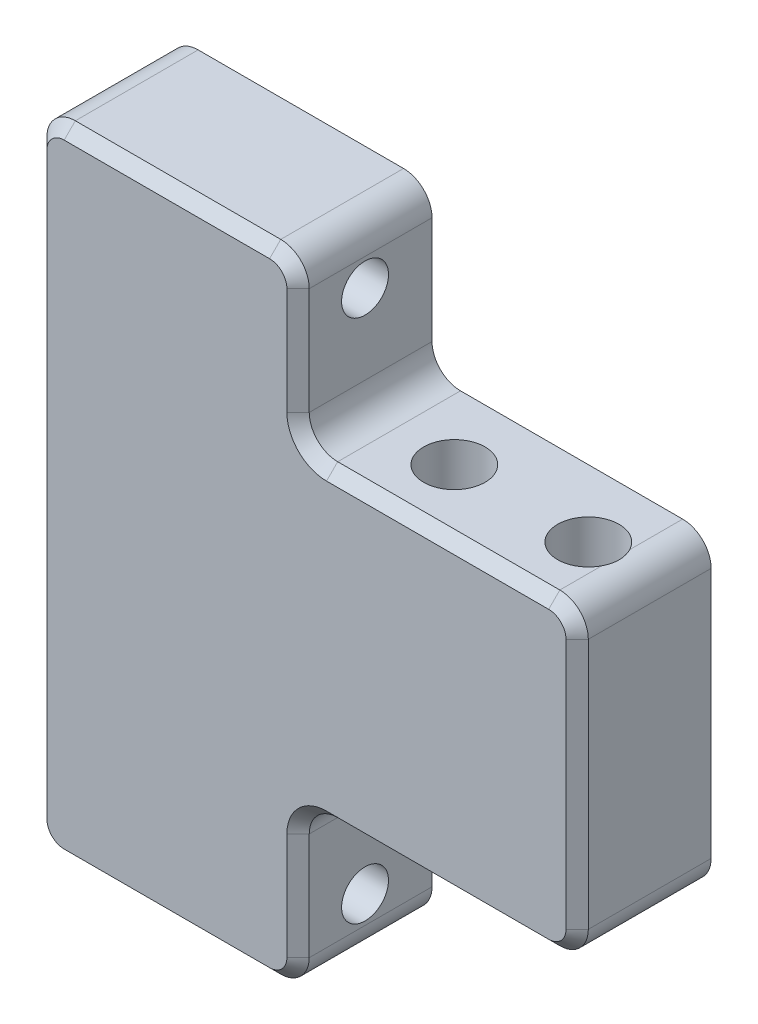
SolidWorks part; units mm, degrees
ref_plane "Front Plane" through (0, 0, 0) normal (0, 0, 1) x (1, 0, 0)
ref_plane "Top Plane" through (0, 0, 0) normal (0, 1, 0) x (1, 0, 0)
ref_plane "Right Plane" through (0, 0, 0) normal (1, 0, 0) x (0, 0, -1)
sketch "Sketch1" plane through (0, 0, 0) normal (0, 0, 1) x (1, 0, 0)
  line L7 (10, 65) -> (10, 8)
  line L9 (33.5, 50.3) -> (33.5, 65)
  line L10 (33.5, 50.3) -> (58.5, 50.3)
  line L11 (10, 8) -> (33.5, 8)
  line L12 (33.5, 8) -> (33.5, 22.7)
  line L13 (10, 65) -> (33.5, 65)
  line L16 (33.5, 22.7) -> (58.5, 22.7)
  line L20 (58.5, 50.3) -> (58.5, 22.7)
extrude "Boss-Extrude1" add sketch "Sketch1" against normal blind 12
sketch "Sketch2" plane through (10, 0, 0) normal (-1, 0, 0) x (0, 0, 1)
  circle A0 centre (-6, 13) radius 2.1
  circle A1 centre (-6, 60) radius 2.1
extrude "Cut-Extrude1" cut sketch "Sketch2" against normal through all
sketch "Sketch3" plane through (0, 22.7, 0) normal (0, -1, 0) x (1, 0, 0)
  circle A0 centre (53.5, -6) radius 5
  circle A1 centre (41.5, -6) radius 5
hole_wizard "M5 Clearance Hole1" positions "Sketch4" profile "Sketch6" hole size "M5" standard "ANSI Metric"
sketch "Sketch4" plane through (0, 22.7, 0) normal (0, -1, 0) x (-1, 0, 0)
  point P0 (-53.5, 6)
  point P3 (-41.5, 6)
sketch "Sketch6" plane through (53.5, 22.7, -6) normal (1, 0, 0) x (0, 0, -1)
  line L0 (0, 0) -> (0, 30)
  line L1 (0, 30) -> (2.75, 28.3476)
  line L2 (2.75, 28.3476) -> (2.75, 0)
  line L5 (2.75, 0) -> (0, 0)
  line L10 (0, 30) -> (-2.75, 28.3476) construction
  line L11 (0, -6.35) -> (0, 107.95) construction
  dimension "Hole Dia." = 5.5
  dimension "Hole Depth" = 30
  dimension "Drill Angle" = 118
fillet "Fillet1" radius 2.55 8 edges at (58.5, 50.3, -6) (33.5, 50.3, -6) (33.5, 65, -6) (10, 65, -6) (10, 8, -6) (33.5, 8, -6) (33.5, 22.7, -6) (58.5, 22.7, -6)
chamfer "Chamfer1" distance 1 angle 45 16 edges at (57.7531, 23.4469, 0) (46, 22.7, 0) (34.2469, 21.9531, 0) (33.5, 15.35, 0) (32.7531, 8.7469, 0) (21.75, 8, 0) (10.7469, 8.7469, 0) (10, 36.5, 0) (10.7469, 64.2531, 0) (21.75, 65, 0) (32.7531, 64.2531, 0) (33.5, 57.65, 0) (34.2469, 51.0469, 0) (46, 50.3, 0) (57.7531, 49.5531, 0) (58.5, 36.5, 0)
